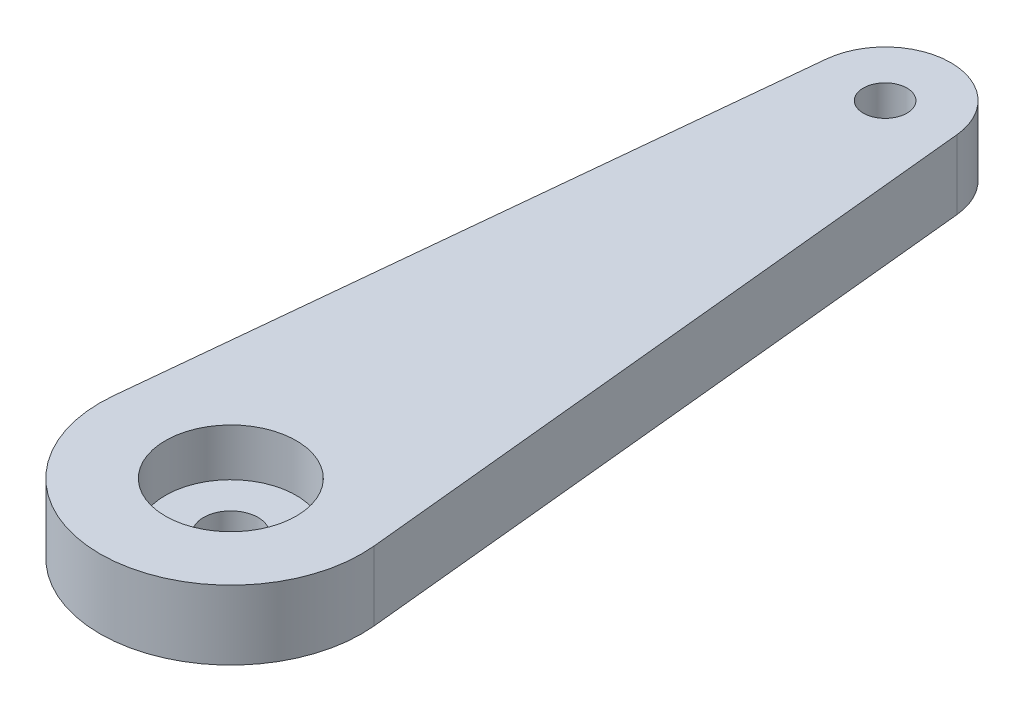
SolidWorks part; units mm, degrees
ref_plane "Front Plane" through (0, 0, 0) normal (0, 0, 1) x (1, 0, 0)
ref_plane "Top Plane" through (0, 0, 0) normal (0, 1, 0) x (1, 0, 0)
ref_plane "Right Plane" through (0, 0, 0) normal (1, 0, 0) x (0, 0, -1)
sketch "Sketch2" plane through (0, 0, 0) normal (0, 1, 0) x (1, 0, 0)
  line L2 (0, 0) -> (0, 30) construction
  line L3 (-3, 30.3) -> (-5.9702, 0.597)
  line L4 (3, 30.3) -> (5.9702, 0.597)
  circle A0 centre (0, 0) radius 1.25
  circle A1 centre (0, 30) radius 1
  arc A2 (-3, 30.3) -> (3, 30.3) centre (0, 30) cw
  arc A3 (-5.9702, 0.597) -> (5.9702, 0.597) centre (0, 0) ccw
  circle A4 centre (0, 0) radius 3
  dimension "D1" = 2.5
  dimension "D2" = 2
  dimension "D6" = 6
  dimension "D5" = 3
  dimension "D3" = 30
  dimension "D4" = 3
extrude "Boss-Extrude1" add sketch "Sketch2" along normal blind 3.175 contours L3 A3 L4 A2 A4 A1 | L3 A3 L4 A2 | A1 | A4 region at (0, 0, -12.3247)
extrude "Boss-Extrude2" add sketch "Sketch2<4>" along normal blind 1 contours A0 A4 region at (-2.9151, 0, 0)
sketch "Sketch2<4>" plane through (0, 0, 0) normal (0, 1, 0) x (1, 0, 0) same geometry as "Sketch2"
sketch "Sketch6" plane through (0, 0, 0) normal (0, 1, 0) x (1, 0, 0)
  line L0 (0, 0) -> (0, 30) construction
ref_axis "Axis1" through (0, 0, 0) along (0, 0, -1)
